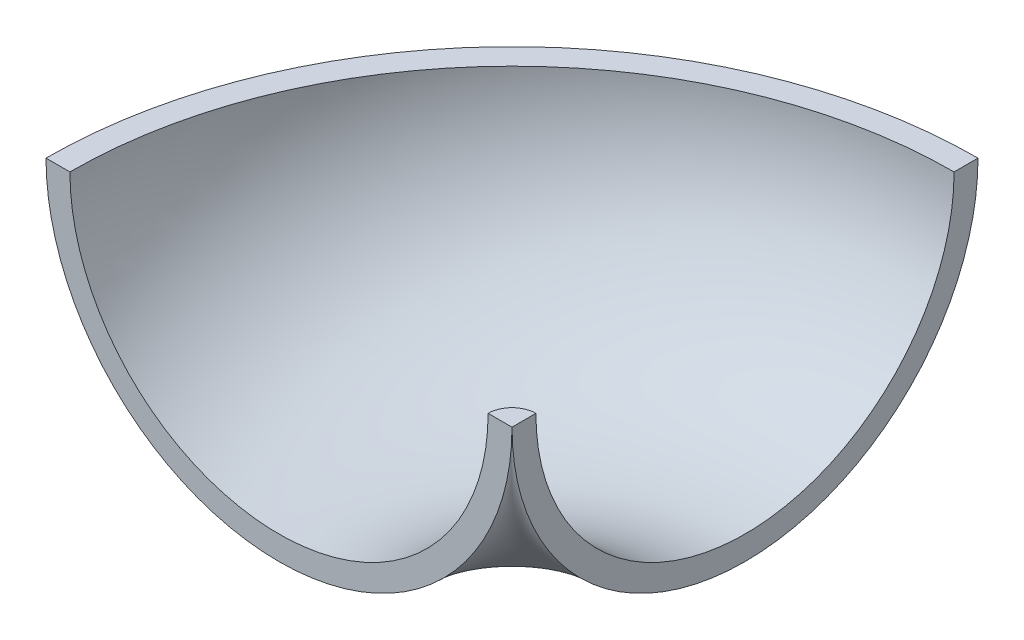
SolidWorks part; units mm, degrees
ref_plane "Front Plane" through (0, 0, 0) normal (0, 0, 1) x (1, 0, 0)
ref_plane "Top Plane" through (0, 0, 0) normal (0, 1, 0) x (1, 0, 0)
ref_plane "Right Plane" through (0, 0, 0) normal (1, 0, 0) x (0, 0, -1)
sketch "Sketch16" plane through (0, 0, 0) normal (0, 1, 0) x (1, 0, 0)
  line L0 (-21.45, 0) -> (21.45, 0) construction
  arc A0 (-39, 0) -> (0, 39) centre (0, 0) cw
  dimension "D1" = 39
sketch "Sketch17" plane through (0, 0, 0) normal (0, 0, 1) x (1, 0, 0)
  line L0 (21.45, 0) -> (-21.45, 0) construction
  line L1 (0, 0) -> (-39, 0) construction
  line L2 (-78, 0) -> (-74, 0)
  line L3 (-4, 0) -> (0, 0)
  arc A0 (0, 0) -> (-78, 0) centre (-39, 0) cw
  arc A1 (-4, 0) -> (-74, 0) centre (-39, 0) cw
  dimension "D1" = 39
  dimension "D2" = 35
sweep "Sweep2" add profiles "Sketch17" path "Sketch16"
